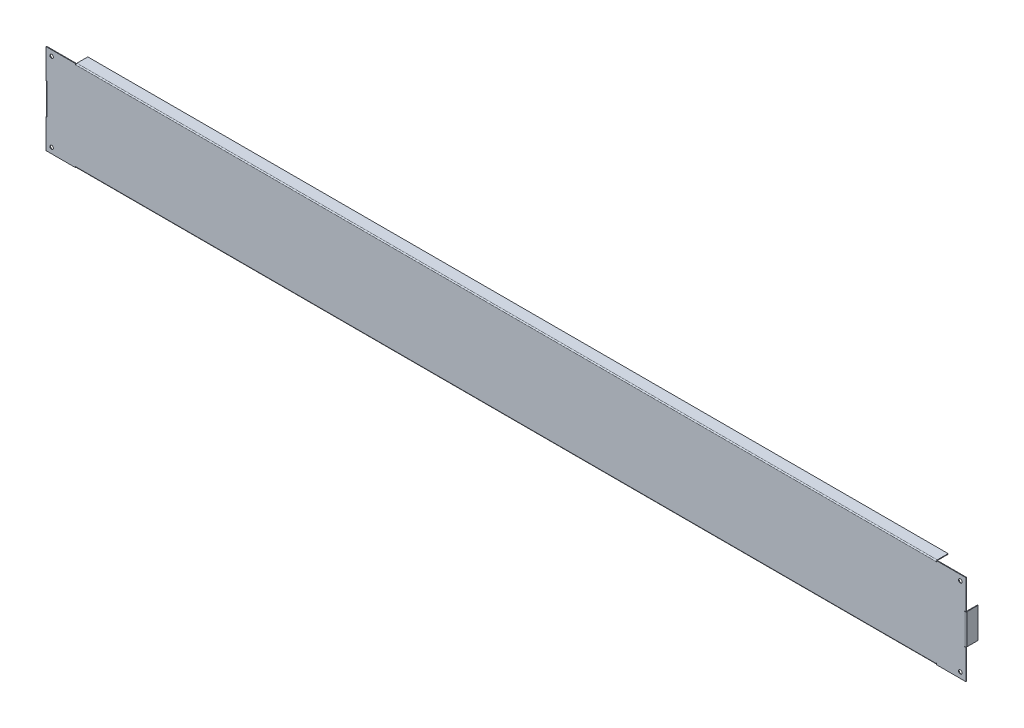
SolidWorks part; units mm, degrees
note: The reader was unsure of these and kept them because the rebuilt part matched: flange length of "边线-法兰1", "边线-法兰2", "边线-法兰3", "边线-法兰4".
ref_plane "前视基准面" through (0, 0, 0) normal (0, 0, 1) x (1, 0, 0)
ref_plane "上视基准面" through (0, 0, 0) normal (0, 1, 0) x (1, 0, 0)
ref_plane "右视基准面" through (0, 0, 0) normal (1, 0, 0) x (0, 0, -1)
sketch "草图1" plane through (0, 0, 0) normal (0, 0, 1) x (1, 0, 0)
  line L1 (-770.5, 75.5) -> (770.5, 75.5)
  line L2 (-770.5, 75.5) -> (-770.5, -75.5)
  line L3 (-770.5, -75.5) -> (770.5, -75.5)
  line L4 (770.5, 75.5) -> (770.5, -75.5)
  line L5 (-770.5, 75.5) -> (770.5, -75.5) construction
  line L6 (-770.5, -75.5) -> (770.5, 75.5) construction
  point P0 (0, 0)
  dimension "D1" = 1541
  dimension "D2" = 151
sheet metal parameters "钣金1" thickness 1 parameters "D1"=0.7366
base flange "基体-法兰1" sketch "草图1" thickness 1 reverse thickness direction no parameters "D1"=0.7366
edge flange "边线-法兰1" sketch "草图5" flange angle 90 flange length 19 flange position material inside bend radius 0.7366 thickness 1 relief rectangular parameters "D6"=10
sketch "草图5" plane through (0, 75.5, -1) normal (0, 1, 0) x (1, 0, 0)
  line L0 (770.5, 0) -> (-770.5, 0) construction
  line L1 (720.5, 0) -> (-720.5, 0)
  line L2 (-720.5, 0) -> (-720.5, 19)
  line L3 (-720.5, 19) -> (720.5, 19)
  line L4 (720.5, 19) -> (720.5, 0)
  line L5 (-770.5, 0) -> (-770.5, -1) construction
  line L6 (770.5, 0) -> (770.5, -1) construction
  line L7 (770.5, -1) -> (-770.5, -1) construction
  dimension "D1" = 50
  dimension "D2" = 50
  dimension "D3" = 20
bend "边线折弯1" bend radius 0.7366 bend angle 90 parameters "D5"=1
edge flange "边线-法兰2" sketch "草图8" flange angle 90 flange length 19 flange position material inside bend radius 0.7366 thickness 1 relief rectangular parameters "D6"=10
sketch "草图8" plane through (0, -75.5, -1) normal (0, -1, 0) x (-1, 0, 0)
  line L2 (-720.5, 0) -> (-720.5, 19)
  line L3 (-720.5, 19) -> (720.5, 19)
  line L4 (720.5, 19) -> (720.5, 0)
  line L5 (770.5, 0) -> (-770.5, 0) construction
  line L6 (720.5, 0) -> (-720.5, 0)
  line L7 (770.5, 0) -> (770.5, -1) construction
  line L8 (-770.5, 0) -> (-770.5, -1) construction
  line L9 (770.5, -1) -> (-770.5, -1) construction
  dimension "D1" = 50
  dimension "D2" = 50
  dimension "D3" = 20
bend "边线折弯2" bend radius 0.7366 bend angle 90 parameters "D5"=2
edge flange "边线-法兰3" sketch "草图11" flange angle 90 flange length 19 flange position material inside bend radius 0.7366 thickness 1 relief rectangular parameters "D6"=10
sketch "草图11" plane through (770.5, 0, -1) normal (1, 0, 0) x (0, -1, 0)
  line L2 (-25.5, 0) -> (-25.5, 19)
  line L3 (-25.5, 19) -> (25.5, 19)
  line L4 (25.5, 19) -> (25.5, 0)
  line L5 (75.5, 0) -> (-75.5, 0) construction
  line L6 (25.5, 0) -> (-25.5, 0)
  line L7 (75.5, -1) -> (-75.5, -1) construction
  line L8 (75.5, 0) -> (75.5, -1) construction
  line L9 (-75.5, 0) -> (-75.5, -1) construction
  dimension "D1" = 20
  dimension "D2" = 50
  dimension "D3" = 50
bend "边线折弯3" bend radius 0.7366 bend angle 90 parameters "D5"=3
edge flange "边线-法兰4" sketch "草图14" flange angle 90 flange length 19 flange position material inside bend radius 0.7366 thickness 1 relief rectangular parameters "D6"=10
sketch "草图14" plane through (-770.5, 0, -1) normal (-1, 0, 0) x (0, 1, 0)
  line L0 (75.5, 0) -> (-75.5, 0) construction
  line L1 (25.5, 0) -> (-25.5, 0)
  line L2 (-25.5, 0) -> (-25.5, 19)
  line L3 (-25.5, 19) -> (25.5, 19)
  line L4 (25.5, 19) -> (25.5, 0)
  line L5 (75.5, 0) -> (75.5, -1) construction
  line L6 (-75.5, 0) -> (-75.5, -1) construction
  line L7 (75.5, -1) -> (-75.5, -1) construction
  dimension "D1" = 50
  dimension "D2" = 50
  dimension "D3" = 20
bend "边线折弯4" bend radius 0.7366 bend angle 90 parameters "D5"=4
sketch "草图15" plane through (0, 0, 0) normal (0, 0, 1) x (1, 0, 0)
  circle A0 centre (761, 66) radius 3
  circle A1 centre (761, -66) radius 3
  circle A2 centre (-761, 66) radius 3
  circle A3 centre (-761, -66) radius 3
  dimension "D1" = 6
extrude "切除-拉伸1" cut sketch "草图15" against normal through all normal cut yes
flat pattern "平板型式1" [suppressed]
sketch "折弯-线1" plane through (0, 0, 0) normal (0, 1, 0) x (-1, 0, 0)
bend of the flat pattern "展开-<边线折弯1>1"
bend of the flat pattern "展开-<边线折弯2>1"
bend of the flat pattern "展开-<边线折弯3>1"
bend of the flat pattern "展开-<边线折弯4>1"
